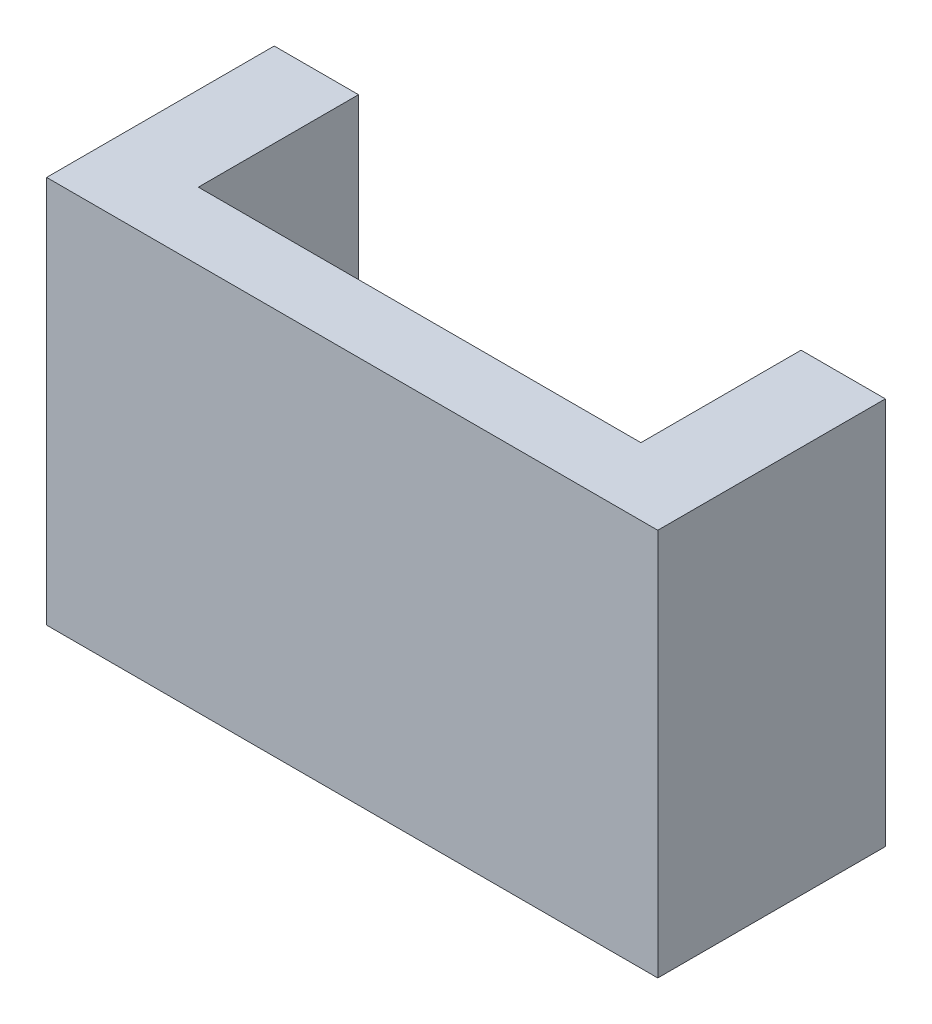
SolidWorks part; units mm, degrees
ref_plane "Спереди" through (0, 0, 0) normal (0, 0, 1) x (1, 0, 0)
ref_plane "Сверху" through (0, 0, 0) normal (0, 1, 0) x (1, 0, 0)
ref_plane "Справа" through (0, 0, 0) normal (1, 0, 0) x (0, 0, -1)
sketch "Эскиз1" plane through (0, 0, 0) normal (0, 0, 1) x (1, 0, 0)
  line L1 (0, 0) -> (10.5, 0)
  line L2 (0, 0) -> (0, -8.6)
  line L3 (0, -8.6) -> (10.5, -8.6)
  line L4 (10.5, 0) -> (10.5, -8.6)
  dimension "D1" = 8.6
  dimension "D2" = 10.5
extrude "Бобышка-Вытянуть1" add sketch "Эскиз1" along normal blind 0.6
sketch "Эскиз2" plane through (0, 0, 0.6) normal (0, 0, 1) x (1, 0, 0)
  line L0 (0, -8.6) -> (10.5, -8.6) construction
  line L1 (0, 0) -> (-2, 0)
  line L2 (0, 0) -> (0, -8.6)
  line L3 (0, -8.6) -> (-2, -8.6)
  line L4 (-2, 0) -> (-2, -8.6)
  line L5 (10.5, 0) -> (12.5, 0)
  line L6 (10.5, 0) -> (10.5, -8.6)
  line L7 (10.5, -8.6) -> (12.5, -8.6)
  line L8 (12.5, 0) -> (12.5, -8.6)
  dimension "D1" = 2
  dimension "D2" = 2
extrude "Бобышка-Вытянуть2" add sketch "Эскиз2" against normal blind 5.4
sketch "Эскиз3" plane through (0, -8.6, 0) normal (0, -1, 0) x (1, 0, 0)
  line L4 (10.5, 0) -> (10.5, -4.8)
  line L8 (0, 0) -> (10.5, 0)
  line L10 (10.5, 0) -> (10.5, -4.8)
  line L12 (12.5, 0.6) -> (-2, 0.6)
  line L16 (0, 0) -> (10.5, 0)
  line L20 (12.5, 0.6) -> (-2, 0.6)
  line L28 (10.5, -4.8) -> (12.5, -4.8)
  line L30 (10.5, -4.8) -> (12.5, -4.8)
  line L32 (12.5, -4.8) -> (12.5, 0.6)
  line L33 (12.5, -4.8) -> (12.5, 0.6)
  line L34 (-2, 0.6) -> (-2, -4.8)
  line L35 (-2, 0.6) -> (-2, -4.8)
  line L36 (-2, -4.8) -> (0, -4.8)
  line L37 (-2, -4.8) -> (0, -4.8)
  line L38 (0, -4.8) -> (0, 0)
  line L39 (0, -4.8) -> (0, 0)
  dimension "D1" = 0
extrude "Бобышка-Вытянуть3" add sketch "Эскиз3" along normal blind 1
sketch "Эскиз4" plane through (0, 0, 0) normal (0, 0, -1) x (-1, 0, 0)
  line L0 (0, 0) -> (0, -9.6) construction
  line L1 (-10.5, 0) -> (0, 0)
  line L2 (-10.5, 0) -> (-10.5, -1)
  line L3 (-10.5, -1) -> (0, -1)
  line L4 (0, 0) -> (0, -1)
  dimension "D1" = 1
extrude "Бобышка-Вытянуть4" add sketch "Эскиз4" along normal blind 1
chamfer "Фаска1" distance 0.4 angle 45 8 edges at (10.5, -9.6, -2.4) (5.25, -9.6, 0) (0, -9.6, -2.4) (-2, -9.6, -2.1) (5.25, -9.6, 0.6) (12.5, -9.6, -2.1) (-1, -9.6, -4.8) (11.5, -9.6, -4.8)
